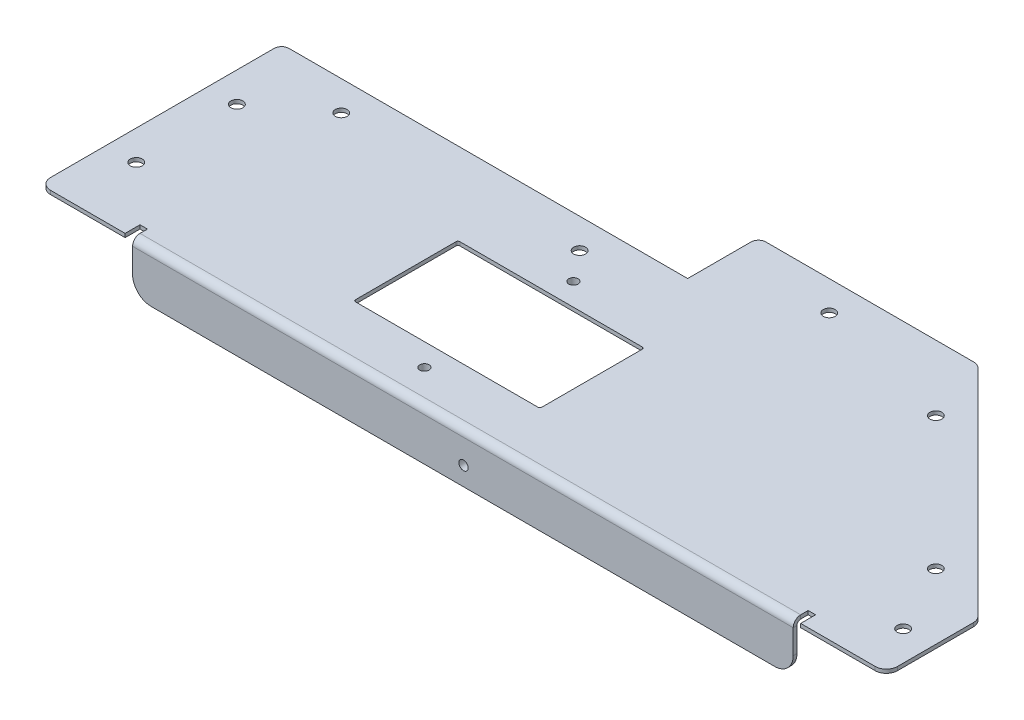
SolidWorks part; units mm, degrees
note: The reader was unsure of these and kept them because the rebuilt part matched: flange length of "边线-法兰1".
material "普通碳钢"
ref_plane "前视基准面" through (0, 0, 0) normal (0, 0, 1) x (1, 0, 0)
ref_plane "上视基准面" through (0, 0, 0) normal (0, 1, 0) x (1, 0, 0)
ref_plane "右视基准面" through (0, 0, 0) normal (1, 0, 0) x (0, 0, -1)
sketch "草图1" plane through (0, 0, 0) normal (0, 1, 0) x (1, 0, 0)
  line L0 (-322.3775, 0) -> (382.0821, 0) construction
  line L1 (0, 265.763) -> (0, -329.6125) construction
  line L2 (-113.67, 31.388) -> (-113.67, -28.612)
  line L3 (-110.67, -31.612) -> (110.67, -31.612)
  line L4 (113.67, -28.612) -> (113.67, -8.2546)
  line L5 (112.7913, -6.1333) -> (55.1487, 51.5093)
  line L6 (53.0274, 52.388) -> (-2.67, 52.388)
  line L7 (-4.67, 50.388) -> (-4.67, 33.388)
  line L8 (-4.67, 33.388) -> (-111.67, 33.388)
  line L9 (-43.83, 11.388) -> (5.17, 11.388)
  line L10 (5.67, 10.888) -> (5.67, -16.112)
  line L11 (5.17, -16.612) -> (-43.83, -16.612)
  line L12 (-44.33, -16.112) -> (-44.33, 10.888)
  arc A0 (-113.67, -28.612) -> (-110.67, -31.612) centre (-110.67, -28.612) ccw
  arc A1 (110.67, -31.612) -> (113.67, -28.612) centre (110.67, -28.612) ccw
  arc A2 (113.67, -8.2546) -> (112.7913, -6.1333) centre (110.67, -8.2546) ccw
  arc A3 (55.1487, 51.5093) -> (53.0274, 52.388) centre (53.0274, 49.388) ccw
  arc A4 (-4.67, 50.388) -> (-2.67, 52.388) centre (-2.67, 50.388) cw
  arc A5 (-113.67, 31.388) -> (-111.67, 33.388) centre (-111.67, 31.388) cw
  circle A6 centre (-105.67, -13.612) radius 1.6
  circle A7 centre (-105.67, 13.388) radius 1.6
  circle A8 centre (-89.67, 25.388) radius 1.6
  circle A9 centre (-25.67, 25.388) radius 1.6
  circle A10 centre (22.33, 44.388) radius 1.6
  circle A11 centre (60.5163, 34.828) radius 1.6
  circle A12 centre (96.1163, -0.772) radius 1.6
  circle A13 centre (105.67, -19.112) radius 1.6
  arc A14 (5.17, 11.388) -> (5.67, 10.888) centre (5.17, 10.888) cw
  arc A15 (5.67, -16.112) -> (5.17, -16.612) centre (5.17, -16.112) cw
  arc A16 (-43.83, -16.612) -> (-44.33, -16.112) centre (-43.83, -16.112) cw
  arc A17 (-44.33, 10.888) -> (-43.83, 11.388) centre (-43.83, 10.888) cw
  point P24 (54.27, 52.388)
  dimension "D11" = 3
  dimension "D12" = 3.2
  dimension "D21" = 8
  dimension "D27" = 0.5
  dimension "D28" = 2
  dimension "D1" = 65
  dimension "D2" = 109
  dimension "D3" = 19
  dimension "D4" = 58.94
  dimension "D5" = 227.34
  dimension "D6" = 45
  dimension "D7" = 50
  dimension "D8" = 28
  dimension "D9" = 15
  dimension "D10" = 108
  dimension "D13" = 18
  dimension "D14" = 27
  dimension "D15" = 8
  dimension "D16" = 24
  dimension "D17" = 64
  dimension "D18" = 8
  dimension "D19" = 8
  dimension "D20" = 8
  dimension "D22" = 8
  dimension "D23" = 12.5
  dimension "D24" = 35.6
  dimension "D25" = 17.56
  dimension "D26" = 27
base flange "基体-法兰1" sketch "草图1" thickness 1 reverse thickness direction no parameters "D1"=1
sketch "草图2" plane through (0, -1, 0) normal (0, -1, 0) x (1, 0, 0)
  line L0 (5.67, 16.112) -> (5.67, -10.888) construction
  line L2 (5.17, -11.388) -> (-43.83, -11.388) construction
  line L3 (-43.83, 16.612) -> (5.17, 16.612) construction
  circle A0 centre (-19.33, -17.388) radius 3
  circle A1 centre (-19.33, 22.612) radius 3
  dimension "D1" = 6
  dimension "D3" = 6
  dimension "D2" = 25
  dimension "D4" = 6
extrude "凸台-拉伸1" add sketch "草图2" along normal blind 2
hole_wizard "M3 螺纹孔1" positions "草图3" profile "草图4" tap size "M3" standard "GB" end condition through all
sketch "草图3" plane through (0, -3, 0) normal (0, -1, 0) x (-1, 0, 0)
  point P0 (19.33, 17.388)
  point P3 (19.33, -22.612)
sketch "草图4" plane through (-19.33, -3, -17.388) normal (1, 0, 0) x (0, 0, -1)
  line L0 (0, 0) -> (0, 3)
  line L1 (0, 3) -> (1.25, 3)
  line L2 (1.25, 3) -> (1.25, 0)
  line L5 (1.25, 0) -> (0, 0)
  line L11 (0, -6.35) -> (0, 107.95) construction
  dimension "通孔螺纹孔钻头直径" = 2.5
  dimension "通孔螺纹孔钻头深度" = 3
cosmetic thread "孔螺蚊线1"
cosmetic thread "孔螺蚊线2"
edge flange "边线-法兰1" sketch "草图7" flange angle 90 flange length 13.5 flange position material inside bend radius 1 thickness 1 relief rectangular parameters "D6"=10
sketch "草图7" plane through (0, -1, 31.612) normal (0, 0, 1) x (-1, 0, 0)
  line L0 (110.67, 0) -> (-110.67, 0) construction
  line L1 (88.67, 0) -> (-88.67, 0)
  line L2 (-88.67, 0) -> (-88.67, 7.5)
  line L3 (-83.67, 12.5) -> (83.67, 12.5)
  line L4 (88.67, 7.5) -> (88.67, 0)
  line L5 (113.67, 0) -> (113.67, -1) construction
  line L6 (-113.67, 0) -> (-113.67, -1) construction
  line L7 (110.67, -1) -> (-110.67, -1) construction
  arc A0 (-83.67, 12.5) -> (-88.67, 7.5) centre (-83.67, 7.5) ccw
  arc A1 (83.67, 12.5) -> (88.67, 7.5) centre (83.67, 7.5) cw
  dimension "D4" = 5
  dimension "D1" = 25
  dimension "D2" = 25
  dimension "D3" = 13.5
bend "边线折弯1" bend radius 1 bend angle 90 parameters "D5"=1
sketch "草图8" plane through (0, 0, 30.612) normal (0, 0, -1) x (-1, 0, 0)
  line L0 (88.67, 0) -> (-88.67, 0) construction
  line L1 (113.67, -1) -> (113.67, 0) construction
  circle A0 centre (-0.17, -8.5) radius 3
  dimension "D1" = 6
  dimension "D2" = 8.5
  dimension "D3" = 113.84
extrude "凸台-拉伸2" add sketch "草图8" along normal blind 2
hole_wizard "M3 螺纹孔2" positions "草图9" profile "草图10" tap size "M3" standard "GB" end condition through all
sketch "草图9" plane through (0, 0, 28.612) normal (0, 0, -1) x (-1, 0, 0)
  point P0 (-0.17, -8.5)
sketch "草图10" plane through (0.17, -8.5, 28.612) normal (1, 0, 0) x (0, 1, 0)
  line L0 (0, 0) -> (0, 3)
  line L1 (0, 3) -> (1.25, 3)
  line L2 (1.25, 3) -> (1.25, 0)
  line L5 (1.25, 0) -> (0, 0)
  line L11 (0, -6.35) -> (0, 107.95) construction
  dimension "通孔螺纹孔钻头直径" = 2.5
  dimension "通孔螺纹孔钻头深度" = 3
cosmetic thread "孔螺蚊线3"
sketch "折弯-线1" [suppressed] plane through (0, 0, 0) normal (0, 1, 0) x (1, 0, 0)
sketch "边界框1" [suppressed] plane through (0, 0, 0) normal (0, 1, 0) x (1, 0, 0)
sheet metal parameters "钣金6" thickness 1 parameters "D1"=1
flat pattern "平板型式6" [suppressed]
sketch "折弯-线2" plane through (0, 0, 0) normal (0, 1, 0) x (1, 0, 0)
sketch3d "边界框2" [suppressed]
  line L0 (113.67, -31.612, 0) -> (-113.67, -31.612, 0) construction
  line L1 (113.67, 52.388, 0) -> (-113.67, 52.388, 0) construction
  line L2 (113.67, -31.612, 0) -> (113.67, 52.388, 0) construction
  line L3 (-113.67, -31.612, 0) -> (-113.67, 52.388, 0) construction
sheet metal parameters "钣金7" thickness 1 parameters "D1"=1
flat pattern "平板型式6"
sketch "折弯-线2" plane through (0, 0, 0) normal (0, 1, 0) x (1, 0, 0)
sketch3d "边界框2" [suppressed]
  line L0 (113.67, -31.612, 0) -> (-113.67, -31.612, 0) construction
  line L1 (113.67, 52.388, 0) -> (-113.67, 52.388, 0) construction
  line L2 (113.67, -31.612, 0) -> (113.67, 52.388, 0) construction
  line L3 (-113.67, -31.612, 0) -> (-113.67, 52.388, 0) construction
sheet metal parameters "钣金8" thickness 1 parameters "D1"=1
flat pattern "平板型式6"
sketch "折弯-线2" plane through (0, 0, 0) normal (0, 1, 0) x (1, 0, 0)
sketch3d "边界框2" [suppressed]
  line L0 (113.67, -31.612, 0) -> (-113.67, -31.612, 0) construction
  line L1 (113.67, 52.388, 0) -> (-113.67, 52.388, 0) construction
  line L2 (113.67, -31.612, 0) -> (113.67, 52.388, 0) construction
  line L3 (-113.67, -31.612, 0) -> (-113.67, 52.388, 0) construction
sheet metal parameters "钣金9" thickness 1 parameters "D1"=1
flat pattern "平板型式6" [suppressed]
sketch "折弯-线2" plane through (0, 0, 0) normal (0, 1, 0) x (1, 0, 0)
sketch3d "边界框2" [suppressed]
  line L0 (113.67, -31.612, 0) -> (-113.67, -31.612, 0) construction
  line L1 (113.67, 52.388, 0) -> (-113.67, 52.388, 0) construction
  line L2 (113.67, -31.612, 0) -> (113.67, 52.388, 0) construction
  line L3 (-113.67, -31.612, 0) -> (-113.67, 52.388, 0) construction
bend of the flat pattern "展开-<边线折弯1>1"
sheet metal parameters "钣金10" thickness 1 parameters "D1"=1
flat pattern "平板型式6" [suppressed]
sketch "折弯-线2" plane through (0, 0, 0) normal (0, 1, 0) x (1, 0, 0)
sketch3d "边界框2" [suppressed]
  line L0 (113.67, -31.612, 0) -> (-113.67, -31.612, 0) construction
  line L1 (113.67, 52.388, 0) -> (-113.67, 52.388, 0) construction
  line L2 (113.67, -31.612, 0) -> (113.67, 52.388, 0) construction
  line L3 (-113.67, -31.612, 0) -> (-113.67, 52.388, 0) construction
bend of the flat pattern "展开-<边线折弯1>1"
sheet metal parameters "钣金11" thickness 1 parameters "D1"=1
flat pattern "平板型式6"
sketch "折弯-线2" plane through (0, 0, 0) normal (0, 1, 0) x (-1, 0, 0)
  line L0 (88.67, 30.7901) -> (-88.67, 30.7901) construction
  line L1 (88.67, 30.7901) -> (-88.67, 30.7901) construction
sketch3d "边界框2" [suppressed]
  line L0 (3, 14.8562, 0) -> (-224.34, 14.8562, 0) construction
  line L1 (3, -81, 0) -> (-224.34, -81, 0) construction
  line L2 (3, 14.8562, 0) -> (3, -81, 0) construction
  line L3 (-224.34, 14.8562, 0) -> (-224.34, -81, 0) construction
bend of the flat pattern "展开-<边线折弯1>1"
